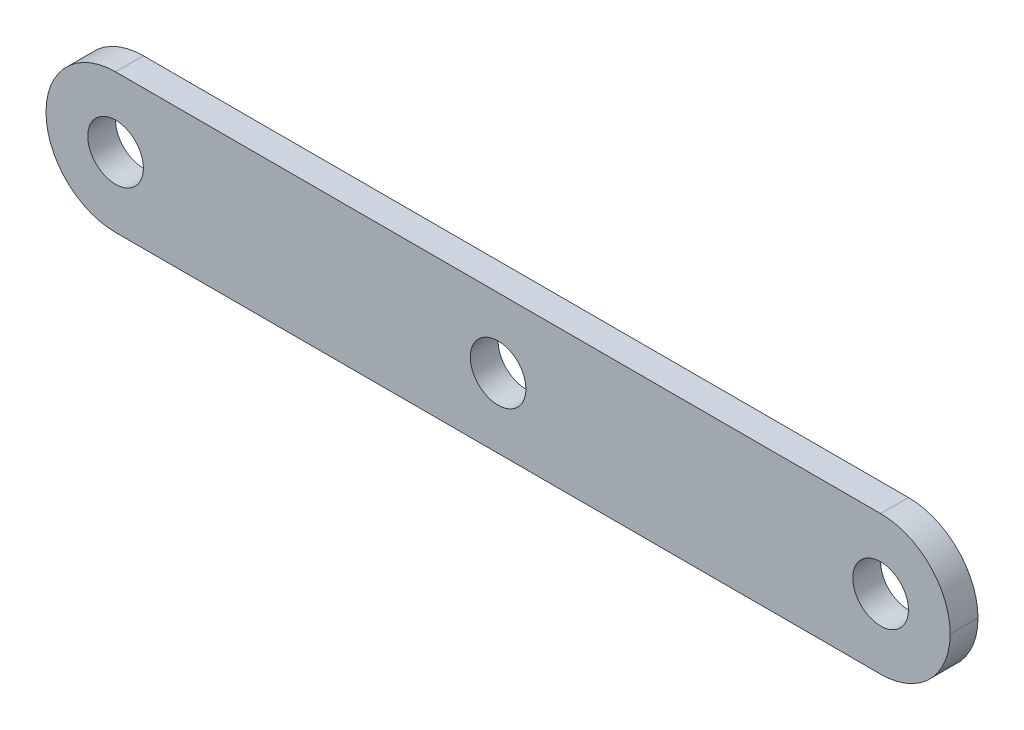
SolidWorks part; units mm, degrees
material "Thornel Mat VMA"
ref_plane "前视基准面" through (0, 0, 0) normal (0, 0, 1) x (1, 0, 0)
ref_plane "上视基准面" through (0, 0, 0) normal (0, 1, 0) x (1, 0, 0)
ref_plane "右视基准面" through (0, 0, 0) normal (1, 0, 0) x (0, 0, -1)
sketch "草图1" plane through (0, 0, 0) normal (0, 0, 1) x (1, 0, 0)
  line L1 (-32.5, -5) -> (32.5, -5)
  line L2 (-32.5, -5) -> (-32.5, 5)
  line L3 (-32.5, 5) -> (32.5, 5)
  line L4 (32.5, -5) -> (32.5, 5)
  line L5 (-32.5, -5) -> (32.5, 5) construction
  line L6 (-32.5, 5) -> (32.5, -5) construction
  point P0 (0, 0)
  dimension "D1" = 65
  dimension "D2" = 10
extrude "凸台-拉伸1" add sketch "草图1" along normal blind 2
fillet "圆角1" radius 5 4 edges at (32.5, -5, 1) (-32.5, -5, 1) (-32.5, 5, 1) (32.5, 5, 1)
sketch "草图3" plane through (0, 0, 2) normal (0, 0, 1) x (1, 0, 0)
  line L0 (0, 4.8774) -> (0, -3.8024) construction
  circle A0 centre (-27.5, 0) radius 2
  circle A1 centre (27.5, 0) radius 2
  circle A2 centre (0, 0) radius 2
  dimension "D1" = 4
  dimension "D2" = 4
extrude "切除-拉伸1" cut sketch "草图3" against normal blind 2
